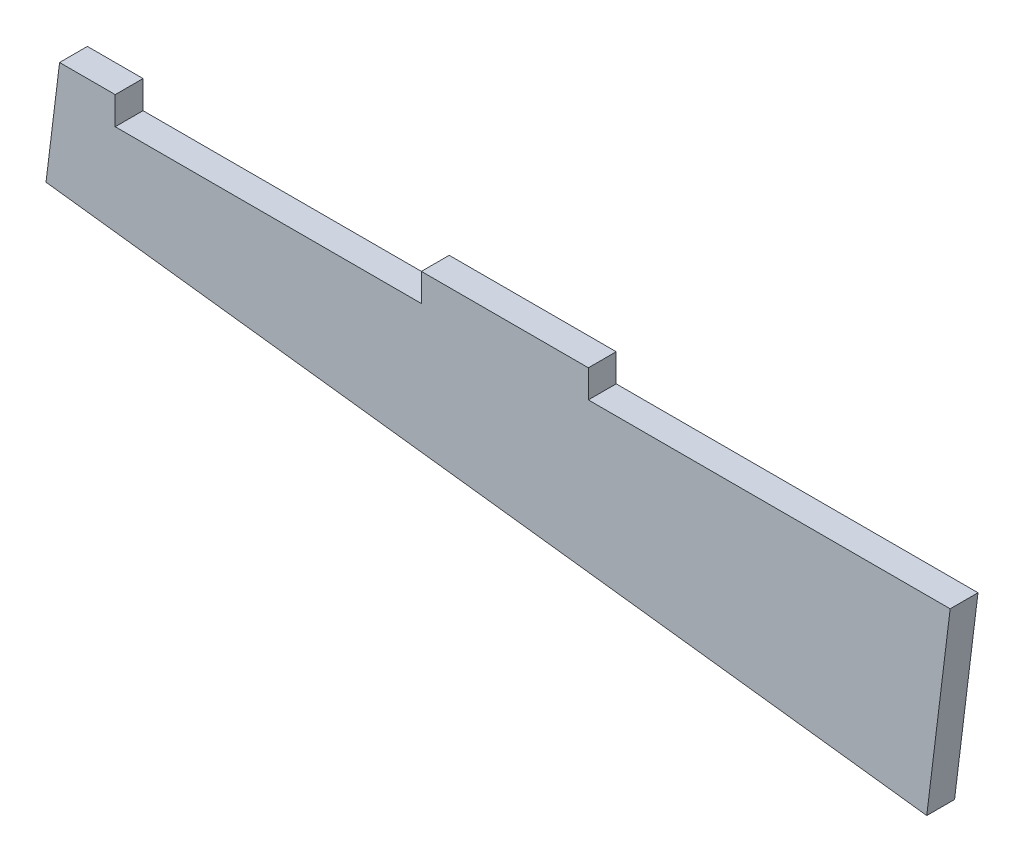
SolidWorks part; units mm, degrees
ref_plane "Front Plane" through (0, 0, 0) normal (0, 0, 1) x (1, 0, 0)
ref_plane "Top Plane" through (0, 0, 0) normal (0, 1, 0) x (1, 0, 0)
ref_plane "Right Plane" through (0, 0, 0) normal (1, 0, 0) x (0, 0, -1)
sketch "Sketch1" plane through (0, 0, 0) normal (0, 0, 1) x (1, 0, 0)
  line L0 (-195.3168, -62.6592) -> (-182.6168, -62.6592)
  line L4 (-182.6168, -62.6592) -> (-182.6168, -69.0092)
  line L5 (-182.6168, -69.0092) -> (-112.7668, -69.0092)
  line L6 (-112.7668, -69.0092) -> (-112.7668, -62.6592)
  line L7 (-112.7668, -62.6592) -> (-74.6668, -62.6592)
  line L8 (-74.6668, -62.6592) -> (-74.6668, -69.0092)
  line L9 (-74.6668, -69.0092) -> (7.8832, -69.0092)
  line L10 (7.8832, -69.0092) -> (2.5379, -112.5435)
  line L11 (2.5379, -112.5435) -> (-198.4122, -87.8699)
  line L12 (-198.4122, -87.8699) -> (-195.3168, -62.6592)
  line L13 (-367.921, -55.3613) -> (25.779, -103.7016) construction
  dimension "D1" = 12.7
  dimension "D2" = 6.35
  dimension "D3" = 69.85
  dimension "D4" = 38.1
  dimension "D5" = 82.55
  dimension "D6" = 25.4
extrude "Boss-Extrude1" add sketch "Sketch1" against normal blind 6.35
